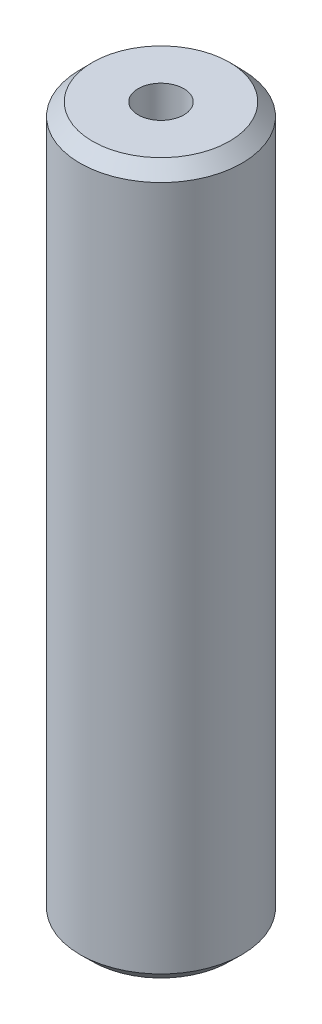
SolidWorks part; units mm, degrees
ref_plane "Front Plane" through (0, 0, 0) normal (0, 0, 1) x (1, 0, 0)
ref_plane "Top Plane" through (0, 0, 0) normal (0, 1, 0) x (1, 0, 0)
ref_plane "Right Plane" through (0, 0, 0) normal (1, 0, 0) x (0, 0, -1)
sketch "Sketch1" plane through (0, 0, 0) normal (0, 1, 0) x (1, 0, 0)
  circle A0 centre (0, 0) radius 5
  dimension "SHAFT_OD" = 10
extrude "Boss-Extrude1" add sketch "Sketch1" along normal blind 43.8845
sketch "Sketch2" plane through (0, 0, 0) normal (0, 1, 0) x (1, 0, 0)
  circle A0 centre (0, 0) radius 1.4091
  dimension "BORE_D" = 2.8182
extrude "Cut-Extrude1" cut sketch "Sketch2" along normal through all
chamfer "Chamfer1" distance 0.7869 angle 44.482 2 edges at (0, 43.8845, 5) (0, 0, 5) first distance on face at (0, 43.8845, 5) first distance on face at (0, 0, 1.4091)
